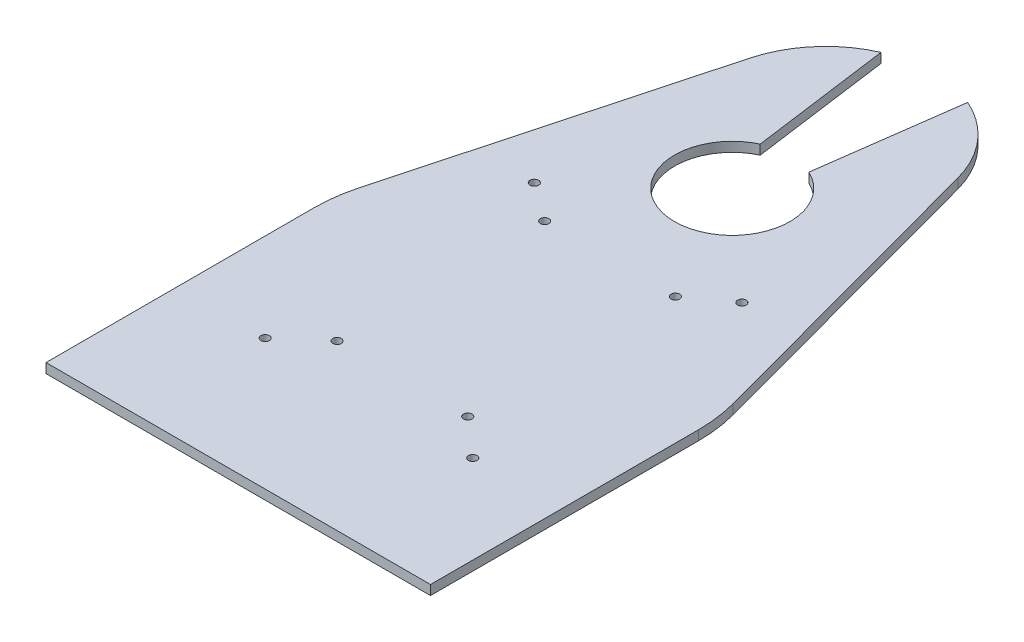
SolidWorks part; units mm, degrees
ref_plane "Front Plane" through (0, 0, 0) normal (0, 0, 1) x (1, 0, 0)
ref_plane "Top Plane" through (0, 0, 0) normal (0, 1, 0) x (1, 0, 0)
ref_plane "Right Plane" through (0, 0, 0) normal (1, 0, 0) x (0, 0, -1)
sketch "Sketch1" plane through (0, 0, 0) normal (0, 1, 0) x (1, 0, 0)
  line L0 (63.5, 144.1169) -> (63.5, 0) construction
  line L1 (0, 0) -> (127, 0)
  line L2 (0, 0) -> (0, 88.5169)
  line L4 (127, 0) -> (127, 88.5169)
  line L9 (63.5, 139.7) -> (63.5, 116.7) construction
  line L10 (1.754, 101.7506) -> (29.1678, 203.3506)
  line L11 (97.8322, 203.3506) -> (125.246, 101.7506)
  line L12 (71.53, 180.4418) -> (77.8191, 226.6367)
  line L13 (55.47, 180.4418) -> (49.1809, 226.6367)
  arc A0 (29.1678, 203.3506) -> (49.1809, 226.6367) centre (63.5, 194.087) cw
  arc A1 (0, 88.5169) -> (1.754, 101.7506) centre (50.8, 88.5169) cw
  arc A2 (125.246, 101.7506) -> (127, 88.5169) centre (76.2, 88.5169) cw
  circle A3 centre (29.21, 43.18) radius 1.4224
  circle A4 centre (29.21, 132.08) radius 1.4224
  circle A5 centre (97.79, 43.18) radius 1.4224
  circle A6 centre (97.79, 132.08) radius 1.4224
  circle A9 centre (85.09, 54.2282) radius 1.4224
  circle A10 centre (85.09, 122.8082) radius 1.4224
  circle A11 centre (41.91, 122.8082) radius 1.4224
  circle A12 centre (41.91, 54.2282) radius 1.4224
  arc A13 (55.47, 180.4418) -> (71.53, 180.4418) centre (63.5, 163.1669) ccw
  arc A14 (77.8191, 226.6367) -> (97.8322, 203.3506) centre (63.5, 194.087) cw
  point P12 (0, 95.25)
  dimension "D4" = 50.8
  dimension "D7" = 68.58
  dimension "D10" = 68.58
  dimension "D1" = 127
  dimension "D2" = 95.25
  dimension "D6" = 101.6
  dimension "D8" = 43.18
  dimension "D9" = 88.9
  dimension "D11" = 43.18
extrude "Boss-Extrude2" add sketch "Sketch1" along normal blind 3.175
